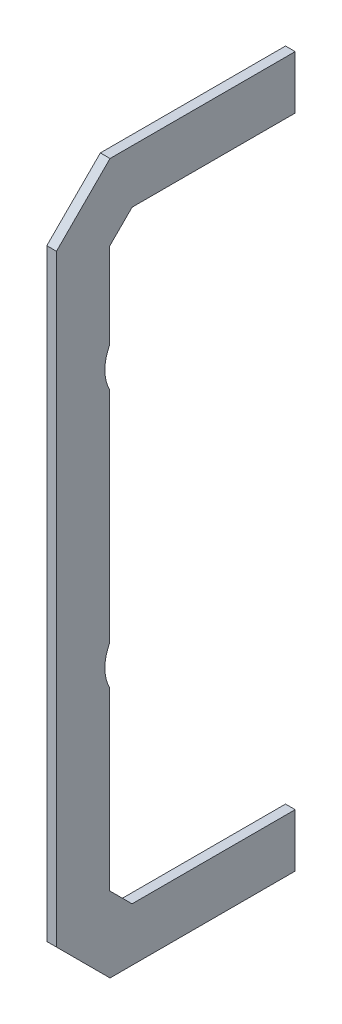
SolidWorks part; units mm, degrees
ref_plane "Front Plane" through (0, 0, 0) normal (0, 0, 1) x (1, 0, 0)
ref_plane "Top Plane" through (0, 0, 0) normal (0, 1, 0) x (1, 0, 0)
ref_plane "Right Plane" through (0, 0, 0) normal (1, 0, 0) x (0, 0, -1)
sketch "Sketch1" plane through (0, 0, 0) normal (1, 0, 0) x (0, 0, -1)
  line L0 (0, 93.4) -> (0, -93.4)
  line L1 (0, -93.4) -> (16.6, -110)
  line L2 (16.6, -110) -> (74, -110)
  line L3 (0, 93.4) -> (16.6, 110)
  line L4 (16.6, 110) -> (74, 110)
  line L5 (74, 110) -> (74, -110) construction
  dimension "D1" = 220
  dimension "D2" = 74
  dimension "D3" = 16.6
extrude "Extrude-Thin1" add sketch "Sketch1" along normal blind 3 thin thin type one direction wall 16.5
sketch "Sketch2" plane through (3, 0, 0) normal (1, 0, 0) x (0, 0, -1)
  line L0 (0, -93.4) -> (0, 93.4) construction
  line L1 (28, -26) -> (28, 54) construction
  circle A0 centre (28, 54) radius 13
  circle A1 centre (28, -26) radius 13
  dimension "D1" = 80
  dimension "D2" = 54
  dimension "D3" = 26
  dimension "D4" = 28
extrude "Cut-Extrude1" cut sketch "Sketch2" against normal through all
